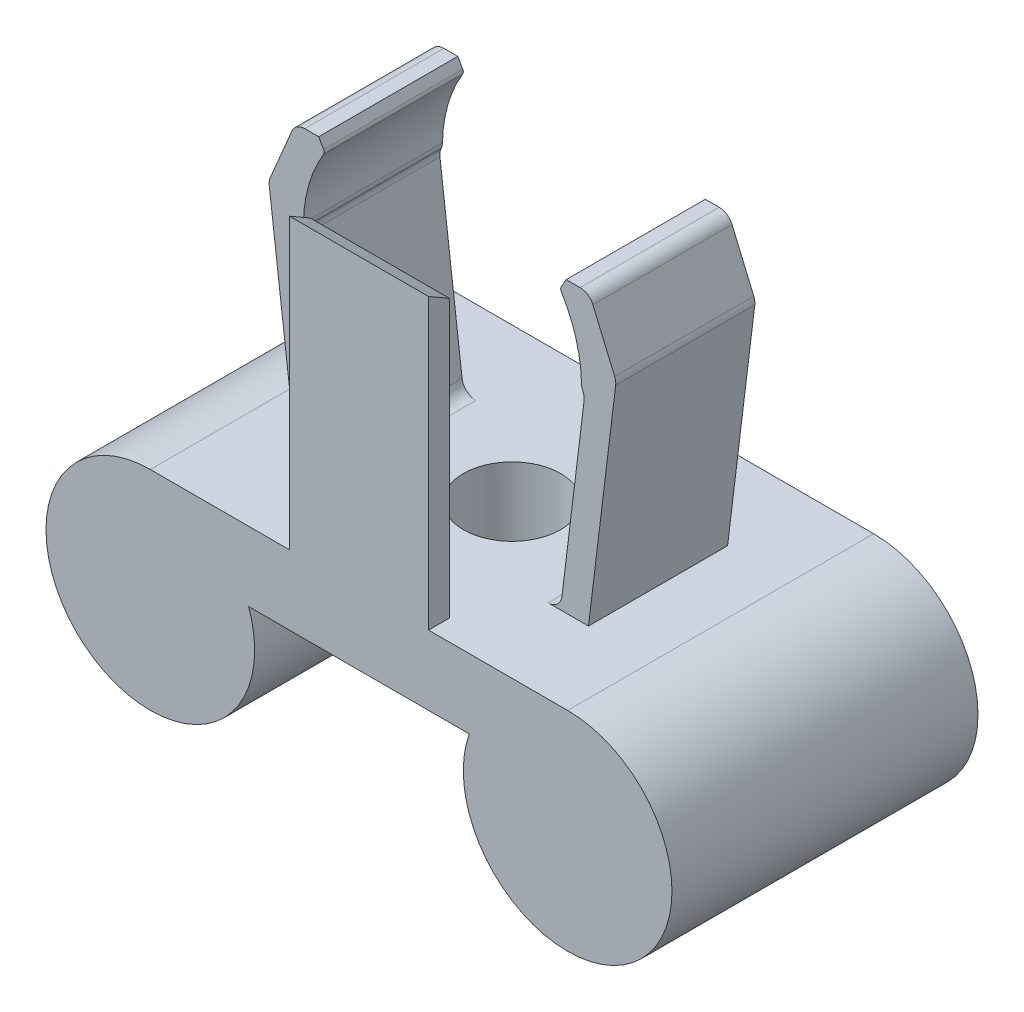
SolidWorks part; units mm, degrees
ref_plane "Спереди" through (0, 0, 0) normal (0, 0, 1) x (1, 0, 0)
ref_plane "Сверху" through (0, 0, 0) normal (0, 1, 0) x (1, 0, 0)
ref_plane "Справа" through (0, 0, 0) normal (1, 0, 0) x (0, 0, -1)
sketch "Эскиз1" plane through (0, 0, 0) normal (0, 0, 1) x (1, 0, 0)
  line L0 (9, 0) -> (-9, 0)
  line L1 (-9.9925, 0.8778) -> (-10.5, 5)
  line L7 (-10.5, 5) -> (10.5, 5)
  line L8 (0, 34.577) -> (0, 0) construction
  line L12 (9.9925, 0.8778) -> (10.5, 5)
  arc A5 (-9, 0) -> (-9.9925, 0.8778) centre (-9, 1) cw
  arc A16 (9, 0) -> (9.9925, 0.8778) centre (9, 1) ccw
  point P2 (0, 0)
  point P4 (7.5, 5)
  point P5 (0, 0)
  point P7 (0, 0)
  point P8 (7.5, 5)
  point P14 (-10.3944, 5)
  dimension "D2" = 18
  dimension "D12" = 1
  dimension "D3" = 21
  dimension "D4" = 5
extrude "Основа" add sketch "Эскиз1" along normal blind 11 and the other way blind 11
sketch "Эскиз6" plane through (0, 0, 0) normal (0, 0, 1) x (1, 0, 0)
  line L0 (9, 0) -> (-9, 0)
  line L1 (-9.9926, 0.8784) -> (-12.4532, 20.9676)
  line L2 (-10.8169, 25.1617) -> (-12.381, 21.4801)
  line L3 (-10.0776, 19.4681) -> (-10.1102, 19.3915)
  line L4 (-9.8965, 25.7707) -> (-8.8965, 25.7707)
  line L5 (-8.8965, 25.7707) -> (-8.5402, 25.1534)
  line L6 (-10.1824, 18.8789) -> (-8.59, 5.8784)
  line L7 (-7.5975, 5) -> (7.5975, 5)
  line L8 (0, 6.8105) -> (0, 0) construction
  line L9 (-10, 18) -> (-10, 19.6508) construction
  line L10 (10.0776, 19.4681) -> (10.1102, 19.3915)
  line L11 (10.1824, 18.8789) -> (8.59, 5.8784)
  line L12 (9.9926, 0.8784) -> (12.4532, 20.9676)
  line L13 (10.8169, 25.1617) -> (12.381, 21.4801)
  line L14 (9.8965, 25.7707) -> (8.8965, 25.7707)
  line L15 (8.8965, 25.7707) -> (8.5402, 25.1534)
  line L17 (-10.5, 5) -> (-9.9925, 0.8778) construction
  arc A0 (-9.9982, 19.8401) -> (-8.5437, 24.8475) centre (0, 19.6508) cw
  circle A1 centre (0, 18) radius 10 construction
  arc A2 (-8.5437, 24.8475) -> (-8.5402, 25.1534) centre (-8.8, 25.0034) ccw
  arc A3 (-9, 0) -> (-9.9926, 0.8784) centre (-9, 1) cw
  arc A4 (-10.8169, 25.1617) -> (-9.8965, 25.7707) centre (-9.8965, 24.7707) cw
  arc A5 (-12.4532, 20.9676) -> (-12.381, 21.4801) centre (-11.4606, 21.0891) cw
  arc A6 (-7.5975, 5) -> (-8.59, 5.8784) centre (-7.5975, 6) cw
  arc A7 (-10.1824, 18.8789) -> (-10.1102, 19.3915) centre (-9.1898, 19.0005) cw
  arc A8 (-10.0776, 19.4681) -> (-9.9982, 19.8401) centre (-10.998, 19.8591) ccw
  arc A9 (8.5437, 24.8475) -> (8.5402, 25.1534) centre (8.8, 25.0034) cw
  arc A10 (9.9982, 19.8401) -> (8.5437, 24.8475) centre (0, 19.6508) ccw
  arc A11 (10.0776, 19.4681) -> (9.9982, 19.8401) centre (10.998, 19.8591) cw
  arc A12 (10.1824, 18.8789) -> (10.1102, 19.3915) centre (9.1898, 19.0005) ccw
  arc A13 (7.5975, 5) -> (8.59, 5.8784) centre (7.5975, 6) ccw
  arc A14 (9, 0) -> (9.9926, 0.8784) centre (9, 1) ccw
  arc A15 (12.4532, 20.9676) -> (12.381, 21.4801) centre (11.4606, 21.0891) ccw
  arc A16 (10.8169, 25.1617) -> (9.8965, 25.7707) centre (9.8965, 24.7707) ccw
  point P51 (0, 0)
  point P52 (0, 0)
  point P53 (-8.5, 25)
  point P54 (0, 0)
  point P55 (-22.7308, -7.4197)
  point P56 (0, 0)
  point P57 (0, 0)
  point P58 (0, 0)
  point P59 (0, 0)
  point P60 (0, 0)
  point P61 (0, 0)
  point P62 (0, 0)
  point P64 (0, 0)
  point P67 (-10, 0.9387)
  dimension "D1" = 10
  dimension "D6" = 0.3
  dimension "D7" = 1
  dimension "D2" = 5
  dimension "D3" = 2
  dimension "D4" = 60
  dimension "D5" = 30
  dimension "D8" = 13
  dimension "D10" = 8.5
  dimension "D11" = 1
  dimension "D12" = 4
  dimension "D13" = 7
extrude "Боковые толкатели" add sketch "Эскиз6" along normal blind 5 and the other way blind 5
sketch "Эскиз3" plane through (0, 0, 0) normal (1, 0, 0) x (0, 0, -1)
  line L0 (-9.5, 5) -> (-11, 5)
  line L1 (5, 25.7707) -> (-5, 25.7707) construction
  line L2 (-11, 5) -> (-11, 25.7707)
  line L3 (-11, 25.7707) -> (-9.5, 24.9047)
  line L4 (-9.5, 24.9047) -> (-9.5, 5)
  point P2 (0, 0)
  point P3 (0, 0)
  point P4 (-18.1733, 4.4071)
  point P6 (0, 0)
  point P8 (0, 0)
  point P10 (-18.5, 25.3787)
  point P11 (0, 0)
  point P13 (0, 0)
  dimension "D1" = 1.5
  dimension "D2" = 120
extrude "Упор от выпадения сверху" add sketch "Эскиз3" along normal blind 5 and the other way blind 5
sketch "Эскиз4" plane through (0, 0, 0) normal (0, -1, 0) x (1, 0, 0)
  circle A0 centre (0, 0) radius 3.5
  point P4 (0, 0)
  point P8 (0, 0)
  point P10 (0, 4.75)
  dimension "D1" = 7
extrude "Вырез под толкатель" cut sketch "Эскиз4" against normal up to next
sketch "Эскиз7" plane through (0, 0, -11) normal (0, 0, -1) x (-1, 0, 0)
  line L0 (7.9289, 0) -> (9, 0)
  line L1 (9, 0) -> (-9, 0) construction
  line L2 (15, 5) -> (10.5, 5)
  line L4 (10.5, 5) -> (9.9925, 0.8778)
  line L5 (-10.5, 5) -> (10.5, 5) construction
  line L6 (0, 0) -> (0, 25.7707) construction
  line L7 (5, 25.7707) -> (-5, 25.7707) construction
  line L8 (-15, 5) -> (-10.5, 5)
  line L9 (-10.5, 5) -> (-9.9925, 0.8778)
  line L10 (-7.9289, 0) -> (-9, 0)
  arc A0 (7.9289, 0) -> (15, 5) centre (15, -2.5) ccw
  arc A2 (9.9925, 0.8778) -> (9, 0) centre (9, 1) cw
  arc A3 (9, 0) -> (9.9925, 0.8778) centre (9, 1) ccw construction
  arc A4 (-7.9289, 0) -> (-15, 5) centre (-15, -2.5) cw
  arc A5 (-9.9925, 0.8778) -> (-9, 0) centre (-9, 1) ccw
  dimension "D1" = 15
  dimension "D2" = 15
extrude "Бобышка-Вытянуть5" add sketch "Эскиз7" against normal up to surface (22 mm away) up to face at (0, 7.2921, 11)
